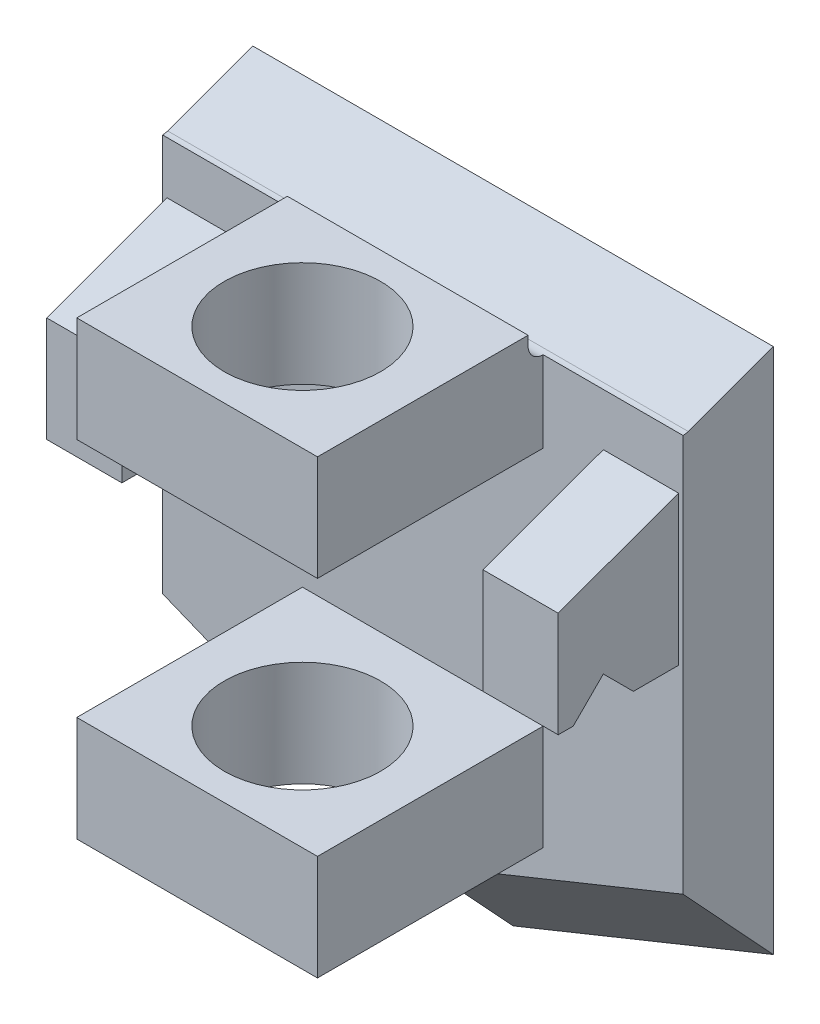
SolidWorks part; units mm, degrees
ref_plane "Plano frontal" through (0, 0, 0) normal (0, 0, 1) x (1, 0, 0)
ref_plane "Plano superior" through (0, 0, 0) normal (0, 1, 0) x (1, 0, 0)
ref_plane "Plano direito" through (0, 0, 0) normal (1, 0, 0) x (0, 0, -1)
sketch "Esboço1" plane through (0, 0, 0) normal (0, 0, 1) x (1, 0, 0)
  line L1 (-17.3, 13) -> (17.3, 13)
  line L2 (-17.3, 13) -> (-17.3, -13)
  line L3 (-17.3, -13) -> (17.3, -13)
  line L4 (17.3, 13) -> (17.3, -13)
  line L5 (-17.3, 13) -> (17.3, -13) construction
  line L6 (-17.3, -13) -> (17.3, 13) construction
  point P0 (0, 0)
  dimension "D1" = 34.6
  dimension "D2" = 26
extrude "Ressalto-extrusão1" add sketch "Esboço1" along normal blind 7
sketch "Esboço10" plane through (0, 0, 0) normal (0, 0, -1) x (-1, 0, 0)
  line L0 (-17.3, -19.5) -> (0, -26.5)
  line L1 (-17.3, 13) -> (17.3, 13)
  line L2 (-17.3, 13) -> (-17.3, 15.5)
  line L3 (-17.3, 15.5) -> (17.3, 15.5)
  line L4 (17.3, 13) -> (17.3, 15.5)
  line L5 (0, -26.5) -> (17.3, -19.5)
  line L6 (-17.3, -19.5) -> (-17.3, -13)
  line L7 (-17.3, -13) -> (17.3, -13)
  line L8 (17.3, -13) -> (17.3, -19.5)
  dimension "D1" = 7
  dimension "D2" = 35
  dimension "D3" = 2.5
extrude "Ressalto-extrusão4" add sketch "Esboço10" against normal up to surface (7 mm away) up to face at (0, 0, 7)
chamfer "Chanfro1" distance 7 angle 45 2 edges at (8.65, -23, 7) (-8.65, -23, 7)
chamfer "Chanfro2" distance 7 angle 20 1 edges at (0, 15.5, 7) first distance on face at (0, 15.5, 3.5)
sketch "Esboço11" plane through (0, 0, 0) normal (0, 1, 0) x (1, 0, 0)
  line L0 (-8, -7) -> (-8, -21)
  line L2 (-8, -21) -> (8, -21)
  line L3 (-8, -7) -> (8, -7)
  line L4 (0, 0) -> (0, -18.2406) construction
  line L5 (-17.3, 0) -> (17.3, 0) construction
  line L6 (8, -7) -> (8, -21)
  line L7 (17.3, -7) -> (-17.3, -7) construction
  circle A0 centre (0, -14) radius 5.2
  point P12 (0, -7)
  point P13 (0, -14)
  dimension "D2" = 5.2
  dimension "D3" = 7
  dimension "D1" = 7
  dimension "D8" = 16
extrude "Ressalto-extrusão5" add sketch "Esboço11" along normal blind 15 and the other way blind 15
sketch "Esboço13" plane through (0, 0, 7) normal (0, 0, 1) x (1, 0, 0)
  line L20 (8, -15) -> (-8, -15)
  line L21 (-8, -15) -> (-8, 12.9522)
  line L22 (-8, 12.9522) -> (-17.3, 12.9522)
  line L23 (-17.3, 12.9522) -> (-17.3, -11.9487)
  line L24 (-17.3, -11.9487) -> (0, -18.9487)
  line L25 (0, -18.9487) -> (17.3, -11.9487)
  line L26 (17.3, -11.9487) -> (17.3, 12.9522)
  line L27 (17.3, 12.9522) -> (8, 12.9522)
  line L28 (8, 12.9522) -> (8, -15)
  line L29 (8, -15) -> (-8, -15)
  line L30 (-8, -15) -> (-8, 18.8455)
  line L31 (-8, 18.8455) -> (-17.3, 18.8455)
  line L32 (-17.3, 18.8455) -> (-17.3, -24.217)
  line L33 (-17.3, -24.217) -> (-0.5703, -24.217)
  line L34 (-0.5703, -24.217) -> (17.3, -21.2474)
  line L35 (17.3, -21.2474) -> (17.3, 18.8455)
  line L36 (17.3, 18.8455) -> (8, 18.8455)
  line L37 (8, 18.8455) -> (8, -15)
  dimension "D1" = 0
extrude "Corte-extrusão2" cut sketch "Esboço13" against normal blind 1
fillet "Filete1" radius 1 1 edges at (0, 12.9522, 7)
sketch "Esboço14" plane through (0, 0, 0) normal (1, 0, 0) x (0, 0, -1)
  line L0 (-6, 9.9118) -> (-14, 7)
  line L1 (-6, 13.3804) -> (-6, -15) construction
  line L2 (-14, 7) -> (-14, 0)
  line L3 (-14, 0) -> (-13, 0)
  line L4 (-13, 0) -> (-11, 2)
  line L5 (-11, 2) -> (-9, 0)
  line L6 (-9, 0) -> (-6, 0)
  line L8 (-6, 0) -> (-6, 9.9118)
  line L9 (-6, -13.0274) -> (-6, 13.3804) construction
  dimension "D1" = 2
  dimension "D2" = 5
  dimension "D3" = 8
  dimension "D4" = 7
  dimension "D5" = 70
extrude "Ressalto-extrusão6" add sketch "Esboço14" along normal blind 5 from offset 12
mirror "Espelhar1" about plane through (0, 0, 0) normal (1, 0, 0) of "Ressalto-extrusão6"
sketch "Esboço15" plane through (0, 0, 21) normal (0, 0, 1) x (1, 0, 0)
  line L0 (8, -15) -> (-8, -15) construction
  line L1 (-9.7066, 8) -> (9.7066, 8)
  line L2 (-9.7066, 8) -> (-9.7066, -8)
  line L3 (-9.7066, -8) -> (9.7066, -8)
  line L4 (9.7066, 8) -> (9.7066, -8)
  line L5 (-9.7066, 8) -> (9.7066, -8) construction
  line L6 (-9.7066, -8) -> (9.7066, 8) construction
  point P0 (0, 0)
  dimension "D1" = 7
extrude "Corte-extrusão3" cut sketch "Esboço15" against normal up to surface (15 mm away) up to face at (14.5, 4.9559, 6)
